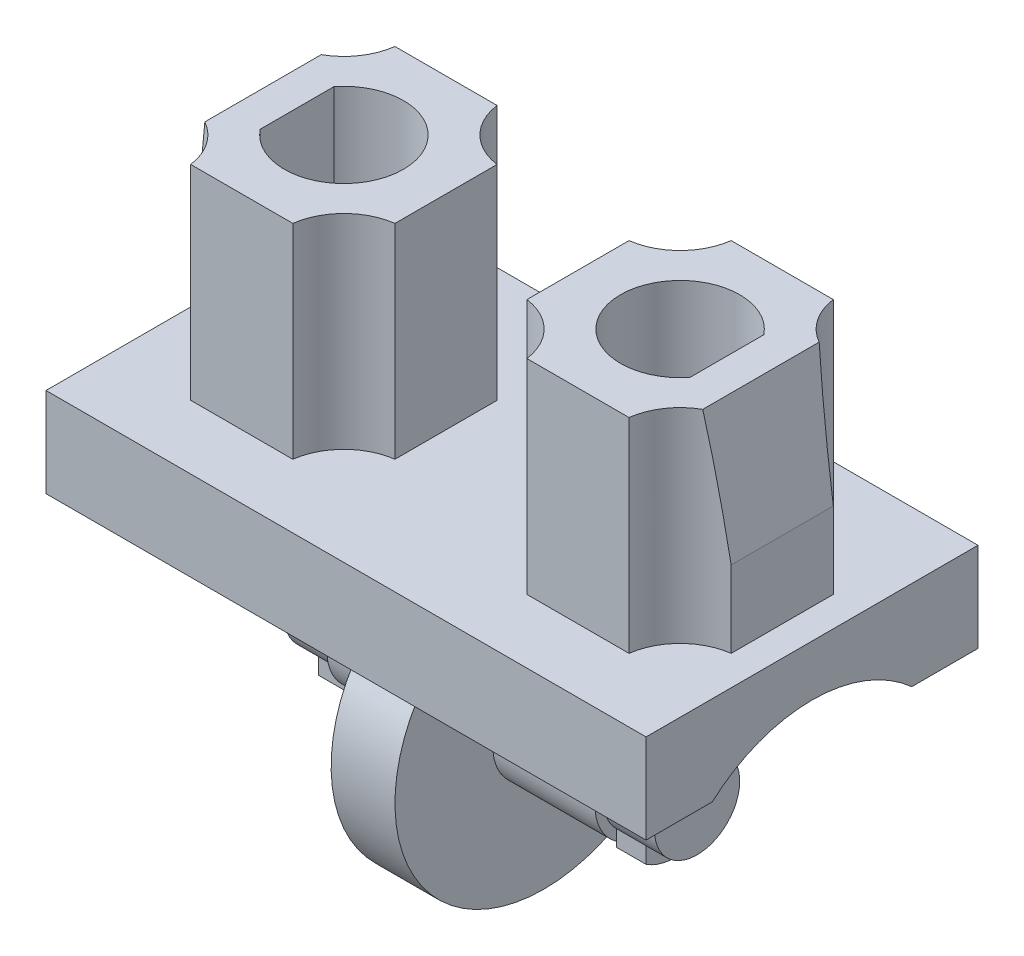
SolidWorks part; units mm, degrees
ref_plane "Alzado" through (0, 0, 0) normal (0, 0, 1) x (1, 0, 0)
ref_plane "Planta" through (0, 0, 0) normal (0, 1, 0) x (1, 0, 0)
ref_plane "Vista lateral" through (0, 0, 0) normal (1, 0, 0) x (0, 0, -1)
sketch "Croquis1" plane through (0, 0, 0) normal (1, 0, 0) x (0, 0, -1)
  line L0 (2.3431, -2.1) -> (3.9, -2.1)
  line L1 (-3.9, 0) -> (3.9, 0)
  line L2 (-3.9, 0) -> (-3.9, -2.1)
  line L3 (-3.9, -2.1) -> (-2.3431, -2.1)
  line L4 (3.9, 0) -> (3.9, -2.1)
  circle A0 centre (0, -4.7) radius 3.5
  dimension "D4" = 7
  dimension "D1" = 7.8
  dimension "D2" = 2.1
  dimension "D3" = 4.7
extrude "Saliente-Extruir1" add sketch "Croquis1" along normal mid plane 14.1 contours A0 L0 L4 L1 L2 L3 region at (0, -0.9029, 0)
extrude "Saliente-Extruir2" add sketch "Croquis1<3>" along normal mid plane 1.5 contours A0 region at (0, -4.7, 0)
sketch "Croquis1<3>" plane through (0, 0, 0) normal (1, 0, 0) x (0, 0, -1) same geometry as "Croquis1"
sketch "Croquis2" plane through (0.75, 0, 0) normal (1, 0, 0) x (0, 0, -1)
  circle A0 centre (0, -4.7) radius 1.2
  dimension "D1" = 2.4
extrude "Saliente-Extruir3" add sketch "Croquis2" along normal blind 2.4
sketch "Croquis3" plane through (3.15, 0, 0) normal (1, 0, 0) x (0, 0, -1)
  circle A0 centre (0, -4.7) radius 1
  dimension "D1" = 2
extrude "Saliente-Extruir4" add sketch "Croquis3" along normal blind 1.2
sketch "Croquis4" plane through (4.35, 0, 0) normal (1, 0, 0) x (0, 0, -1)
  line L0 (-0.6614, -3.95) -> (0.6614, -3.95)
  circle A0 centre (0, -4.7) radius 1 construction
  arc A1 (0.6614, -3.95) -> (-0.6614, -3.95) centre (0, -4.7) ccw
  dimension "D1" = 0.75
extrude "Cortar-Extruir1" cut sketch "Croquis4" against normal up to next
sketch "Croquis5" plane through (3.15, 0, 0) normal (1, 0, 0) x (0, 0, -1)
  line L0 (0, -4.2907) -> (0, -7.3959) construction
  line L1 (-0.7, -5.4141) -> (-0.7, -5.7941)
  line L2 (0.7, -5.4141) -> (0.7, -5.7941)
  arc A0 (-0.6614, -3.95) -> (0.6614, -3.95) centre (0, -4.7) ccw construction
  arc A1 (-0.7, -5.7941) -> (0.7, -5.7941) centre (0, -4.7) ccw
  arc A2 (-0.7, -5.4141) -> (0.7, -5.4141) centre (0, -4.7) ccw
  arc M5 (0.6614, -3.95) -> (-0.6614, -3.95) centre (0, -4.7) cw
  circle M6 centre (0, -4.7) radius 1.2
  dimension "D2" = 0.38
  dimension "D3" = 1.4
extrude "Saliente-Extruir5" add sketch "Croquis5" along normal blind 0.7 contours L0 L2 M5 M6 | L0 A2 L1 M6 | A2 L2 A1 L1 region at (3.15, -5.7137, -0.3648) region at (3.15, -5.7137, 0.3648)
sketch "Croquis6" plane through (0, 0, 0) normal (0, 1, 0) x (1, 0, 0)
  line L0 (1.55, 2.4) -> (0.5664, 3.3836) construction
  line L1 (6.35, -2.4) -> (1.55, -2.4)
  line L2 (6.35, -2.4) -> (6.35, 2.4)
  line L3 (6.35, 2.4) -> (1.55, 2.4)
  line L4 (1.55, -2.4) -> (1.55, 2.4)
  line L5 (6.35, -2.4) -> (1.55, 2.4) construction
  line L6 (6.35, 2.4) -> (1.55, -2.4) construction
  arc A1 (2.75, 2.4) -> (1.55, 1.2) centre (1.3626, 2.5874) cw
  arc A2 (6.35, 1.2) -> (5.15, 2.4) centre (6.5374, 2.5874) cw
  arc A3 (5.15, -2.4) -> (6.35, -1.2) centre (6.5374, -2.5874) cw
  arc A4 (1.55, -1.2) -> (2.75, -2.4) centre (1.3626, -2.5874) cw
  point P0 (3.95, 0)
  point P22 (3.95, 0)
  dimension "D5" = 1.4
  dimension "D1" = 4.8
  dimension "D2" = 4.8
  dimension "D3" = 1.55
  dimension "D4" = 1.2
  dimension "D6" = 4
extrude "Saliente-Extruir6" add sketch "Croquis6" along normal blind 4.8 contours L4 A4 L1 A3 L2 A2 L3 A1 region at (3.95, 0, 0)
sketch "Croquis7" plane through (0, 4.8, 0) normal (0, 1, 0) x (1, 0, 0)
  line L0 (5.15, 2.4) -> (2.75, -2.4) construction
  line L1 (5.05, 0.866) -> (5.05, -0.866)
  line L2 (6.35, -1.2) -> (6.35, 1.2) construction
  arc A0 (5.05, 0.866) -> (5.05, -0.866) centre (3.95, 0) ccw
  dimension "D1" = 2.8
  dimension "D2" = 1.3
extrude "Cortar-Extruir2" cut sketch "Croquis7" against normal blind 4.8 contours L0 A0 | A0 L0 L1 | A0 L1 region at (4.3917, 4.8, 0.3003) region at (3.4186, 4.8, -0.2657)
sketch "Croquis8" plane through (0, 0, 2.4) normal (0, 0, 1) x (1, 0, 0)
  line L0 (5.85, 4.8) -> (6.35, 1.8)
  line L1 (5.85, 4.8) -> (6.35, 4.8)
  line L2 (6.35, 4.8) -> (6.35, 1.8)
  line L3 (6.35, 4.8) -> (5.15, 4.8) construction
  line L4 (6.35, 4.8) -> (6.35, 0) construction
  dimension "D1" = 3
  dimension "D2" = 0.5
extrude "Cortar-Extruir4" cut sketch "Croquis8" against normal blind 4.8
mirror "Simetría1" about plane through (0, 0, 0) normal (1, 0, 0) of "Saliente-Extruir5", "Cortar-Extruir1", "Saliente-Extruir4", "Saliente-Extruir3", "Cortar-Extruir2", "Cortar-Extruir4", "Saliente-Extruir6"
